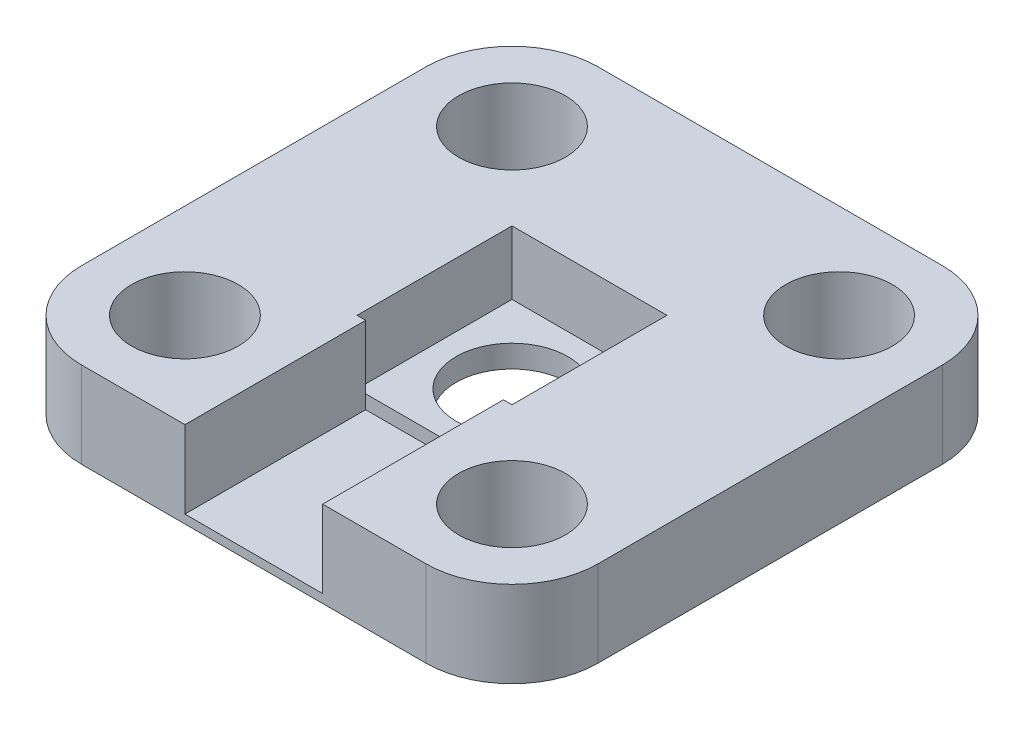
SolidWorks part; units mm, degrees
ref_plane "Front Plane" through (0, 0, 0) normal (0, 0, 1) x (1, 0, 0)
ref_plane "Top Plane" through (0, 0, 0) normal (0, 1, 0) x (1, 0, 0)
ref_plane "Right Plane" through (0, 0, 0) normal (1, 0, 0) x (0, 0, -1)
sketch "Base" plane through (0, 0, 0) normal (0, 1, 0) x (1, 0, 0)
  line L0 (-2, -7.5) -> (-2, -2.25)
  line L1 (-7.5, 7.5) -> (7.5, 7.5)
  line L2 (-7.5, 7.5) -> (-7.5, -7.5)
  line L3 (-7.5, -7.5) -> (7.5, -7.5)
  line L4 (7.5, 7.5) -> (7.5, -7.5)
  line L5 (-7.5, 7.5) -> (7.5, -7.5) construction
  line L6 (-7.5, -7.5) -> (7.5, 7.5) construction
  line L7 (-4.75, 4.75) -> (4.75, 4.75) construction
  line L8 (-4.75, 4.75) -> (-4.75, -4.75) construction
  line L9 (-4.75, -4.75) -> (4.75, -4.75) construction
  line L10 (4.75, 4.75) -> (4.75, -4.75) construction
  line L11 (-4.75, 4.75) -> (4.75, -4.75) construction
  line L12 (-4.75, -4.75) -> (4.75, 4.75) construction
  line L13 (-2.25, 2.25) -> (2.25, 2.25)
  line L14 (-2.25, 2.25) -> (-2.25, -2.25)
  line L15 (-2.25, -2.25) -> (2.25, -2.25)
  line L16 (2.25, 2.25) -> (2.25, -2.25)
  line L17 (-2.25, 2.25) -> (2.25, -2.25) construction
  line L18 (-2.25, -2.25) -> (2.25, 2.25) construction
  line L19 (-2, -2.25) -> (2, -2.25)
  line L20 (2, -2.25) -> (2, -7.5)
  line L21 (0, 0) -> (0, -10.3166) construction
  circle A0 centre (-4.75, 4.75) radius 1.55
  circle A1 centre (4.75, 4.75) radius 1.55
  circle A2 centre (4.75, -4.75) radius 1.55
  circle A3 centre (-4.75, -4.75) radius 1.55
  circle A8 centre (0, 0) radius 1.625
  point P0 (0, 0)
  point P6 (0, 0)
  dimension "D3" = 3.1
  dimension "D4" = 3.25
  dimension "D5" = 4.5
  dimension "D1" = 15
  dimension "D2" = 9.5
  dimension "D6" = 4
extrude "Boss-Extrude1" add sketch "Base" along normal blind 2.5 contours L15 L20 L3 L4 L1 L2 L0 L14 L13 L16 A3 A2 A1 A0 region at (-4.75, 0, 7.2879)
extrude "Boss-Extrude2" add sketch "Sketch1<3>" along normal blind 0.65 contours L16 L13 L14 L15 A8 region at (-2.125, 0, 2.1864)
sketch "Sketch1<3>" plane through (0, 0, 0) normal (0, 1, 0) x (1, 0, 0) same geometry as "Base"
extrude "Boss-Extrude3" add sketch "Sketch1<4>" along normal blind 0.25 contours L20 L15 L0 L3 region at (0, 0, 4.875)
sketch "Sketch1<4>" plane through (0, 0, 0) normal (0, 1, 0) x (1, 0, 0) same geometry as "Base"
fillet "Fillet1" radius 2.5 4 edges at (-7.5, 1.25, 7.5) (-7.5, 1.25, -7.5) (7.5, 1.25, -7.5) (7.5, 1.25, 7.5)
